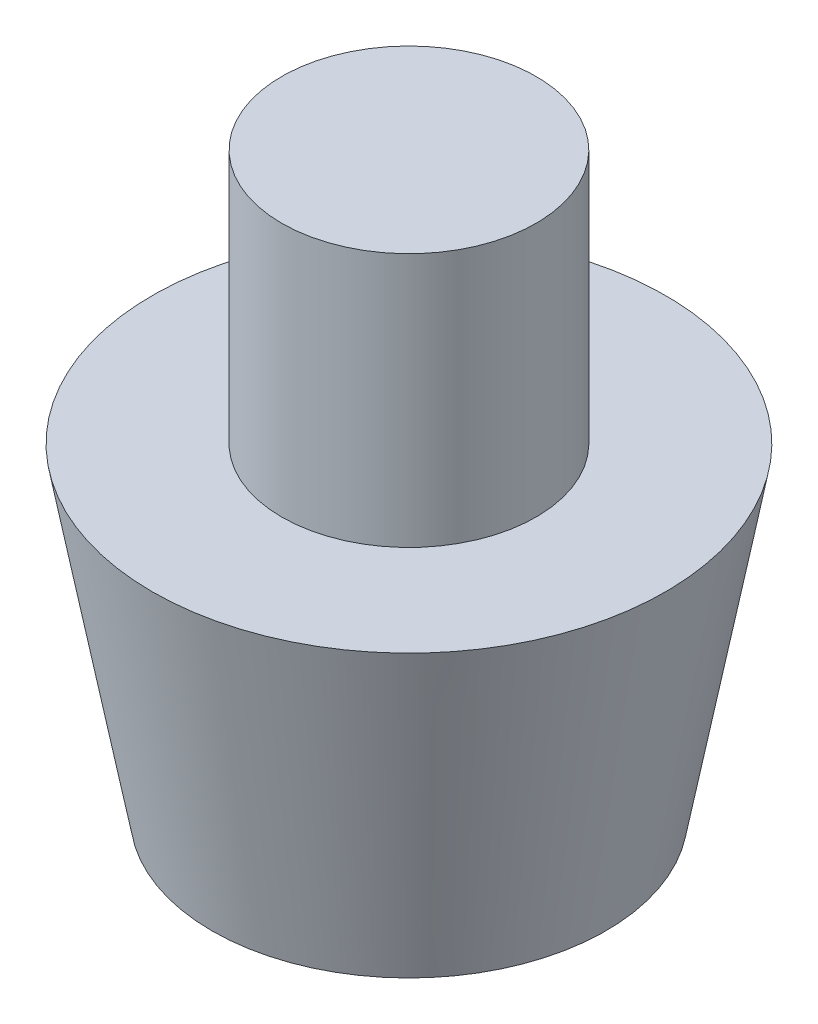
SolidWorks part; units mm, degrees
ref_plane "Front Plane" through (0, 0, 0) normal (0, 0, 1) x (1, 0, 0)
ref_plane "Top Plane" through (0, 0, 0) normal (0, 1, 0) x (1, 0, 0)
ref_plane "Right Plane" through (0, 0, 0) normal (1, 0, 0) x (0, 0, -1)
sketch "Sketch1" plane through (0, 0, 0) normal (0, 0, 1) x (1, 0, 0)
  line L0 (-78.0263, 114.597) -> (-66.3061, 51.0238)
  line L1 (-66.3061, 51.0238) -> (-27.5939, 51.0238)
  line L2 (-27.5939, 51.0238) -> (-27.5939, 114.597)
  line L3 (-27.5939, 114.597) -> (-78.0263, 114.597)
  line L4 (-27.5939, 140.1683) -> (-27.5939, 35.752) construction
revolve "Revolve1" add sketch "Sketch1" angle 360 about L4
sketch "Sketch3" plane through (0, 114.597, 0) normal (0, 1, 0) x (1, 0, 0)
  line L0 (-27.5939, 50.4324) -> (-27.5939, -50.4324) construction
  line L5 (-78.0263, 0) -> (22.8385, 0) construction
  circle A0 centre (-27.5939, 0) radius 25
  circle A1 centre (-27.5939, 0) radius 50.4324 construction
  dimension "D1" = 50
extrude "Boss-Extrude1" add sketch "Sketch3" along normal blind 50
